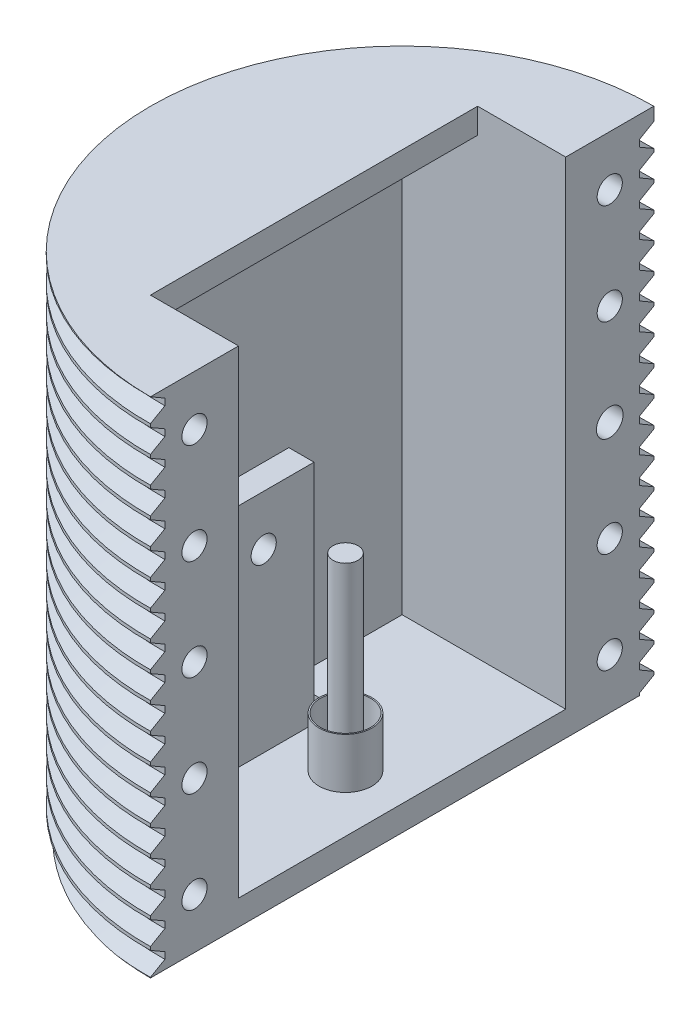
SolidWorks part; units mm, degrees
material "PP Kopolimer"
ref_plane "Front Plane" through (0, 0, 0) normal (0, 0, 1) x (1, 0, 0)
ref_plane "Top Plane" through (0, 0, 0) normal (0, 1, 0) x (1, 0, 0)
ref_plane "Right Plane" through (0, 0, 0) normal (1, 0, 0) x (0, 0, -1)
sketch "Szkic1" plane through (0, 0, 0) normal (0, 1, 0) x (1, 0, 0)
  line L1 (-5, -10) -> (5, -10)
  line L2 (-5, -10) -> (-5, 10)
  line L3 (-5, 10) -> (5, 10)
  line L4 (5, -10) -> (5, 10)
  line L5 (-5, -10) -> (5, 10) construction
  line L6 (-5, 10) -> (5, -10) construction
  point P0 (0, 0)
extrude "Dodanie-wyciągnięcie2" add sketch "Szkic1" along normal blind 1 contours L4 L3 L2 L1
sketch "Szkic2" plane through (0, 1, 0) normal (0, 1, 0) x (1, 0, 0)
  line L1 (-0.5, -2) -> (0.5, -2)
  line L2 (-0.5, -2) -> (-0.5, 2)
  line L3 (-0.5, 2) -> (0.5, 2)
  line L4 (0.5, -2) -> (0.5, 2)
  line L5 (-0.5, -2) -> (0.5, 2) construction
  line L6 (-0.5, 2) -> (0.5, -2) construction
  point P0 (0, 0)
extrude "Wytnij-wyciągnięcie1" cut sketch "Szkic2" against normal blind 1
sketch "Szkic3" plane through (0, 1, 0) normal (0, 1, 0) x (1, 0, 0)
  line L2 (-5, 10) -> (-5, -10)
  line L4 (-1.5, 6.5) -> (-1.5, -6.5)
  line L5 (5, -10) -> (5, 10) construction
  line L8 (-1.5, -6.5) -> (5, -6.5)
  line L9 (5, -10) -> (5, -6.5)
  line L10 (-5, 10) -> (5, 10)
  line L12 (5, 10) -> (5, 6.5)
  line L13 (5, 6.5) -> (-1.5, 6.5)
  line L15 (-5, -10) -> (5, -10)
extrude "Dodanie-wyciągnięcie3" add sketch "Szkic3" along normal blind 19
sketch "Szkic4" plane through (0, 1, 0) normal (0, 1, 0) x (1, 0, 0)
  line L0 (-1.5, -6.5) -> (-1.5, 6.5) construction
  line L1 (-0.5, 2) -> (-1.5, 2)
  line L2 (-0.5, 2) -> (-0.5, -2)
  line L3 (-0.5, -2) -> (-1.5, -2)
  line L4 (-1.5, 2) -> (-1.5, -2)
extrude "Dodanie-wyciągnięcie5" add sketch "Szkic4" along normal blind 8 contours L1 L4 L3 L2
sketch "Szkic7" plane through (-0.5, 0, 0) normal (1, 0, 0) x (0, 0, -1)
  line L0 (0, 9) -> (0, 7) construction
  line L1 (2, 9) -> (-2, 9) construction
  circle A0 centre (0, 7) radius 0.5
extrude "Wytnij-wyciągnięcie2" cut sketch "Szkic7" against normal blind 1 contours A0
sketch "Szkic8" plane through (0, 1, 0) normal (0, 1, 0) x (1, 0, 0)
  line L0 (0.5, 0) -> (5, 0) construction
  line L1 (0.5, -2) -> (0.5, 2) construction
  line L2 (5, -6.5) -> (5, 6.5) construction
  circle A0 centre (2.75, 0) radius 0.5
extrude "Dodanie-wyciągnięcie6" add sketch "Szkic8" along normal blind 7.5
sketch "Szkic13" plane through (-1.5, 0, 0) normal (1, 0, 0) x (0, 0, -1)
  line L0 (-6.5, 20) -> (-6.5, 1) construction
  line L1 (6.5, 20) -> (-6.5, 20)
  line L2 (6.5, 20) -> (6.5, 19)
  line L3 (6.5, 19) -> (-6.5, 19)
  line L4 (-6.5, 20) -> (-6.5, 19)
extrude "Dodanie-wyciągnięcie8" add sketch "Szkic13" along normal blind 3
fillet "Zaokrąglenie2" radius 10 2 edges at (-5, 10, 10) (-5, 10, -10)
sketch "Szkic16" plane through (5, 0, 0) normal (1, 0, 0) x (0, 0, -1)
  line L0 (-8.25, 20) -> (-8.25, 18) construction
  line L1 (-10, 20) -> (-6.5, 20) construction
  line L2 (-8.25, 18) -> (-8.25, 14) construction
  line L3 (-8.25, 14) -> (-8.25, 10) construction
  line L4 (-8.25, 10) -> (-8.25, 6) construction
  line L5 (-8.25, 6) -> (-8.25, 2) construction
  line L6 (-8.25, 2) -> (-8.25, 0) construction
  line L7 (-10, 0) -> (10, 0) construction
  line L8 (8.25, 20) -> (8.25, 18) construction
  line L9 (6.5, 20) -> (10, 20) construction
  line L10 (8.25, 18) -> (8.25, 14) construction
  line L11 (8.25, 14) -> (8.25, 10) construction
  line L12 (8.25, 10) -> (8.25, 6) construction
  line L13 (8.25, 6) -> (8.25, 2) construction
  line L14 (8.25, 2) -> (8.25, 0) construction
  circle A0 centre (-8.25, 18) radius 0.5
  circle A1 centre (-8.25, 14) radius 0.5
  circle A2 centre (-8.25, 10) radius 0.5
  circle A3 centre (-8.25, 6) radius 0.5
  circle A4 centre (-8.25, 2) radius 0.5
  circle A5 centre (8.25, 18) radius 0.5
  circle A6 centre (8.25, 14) radius 0.5
  circle A7 centre (8.25, 10) radius 0.53
  circle A8 centre (8.25, 6) radius 0.5
  circle A9 centre (8.25, 2) radius 0.5
extrude "Wytnij-wyciągnięcie3" cut sketch "Szkic16" against normal blind 2
thread "Gwint1" pitch 1.0583 method cut profile "Profil gwintu1" start angle 270, offset 0, length 20, pitch 1.0583, diameter 20
ref_plane "Płaszczyzna1" through (5, 20, 10) normal (1, 0, 0) x (0, 0, 1)
sketch "Profil gwintu1" plane through (5, 20, 10) normal (1, 0, 0) x (0, 0, 1)
  line L0 (0, 0) -> (0, 1.0583) construction
  line L11 (0, 0) -> (0, 0.926)
  line L12 (0, 0.926) -> (-0.5728, 0.5953)
  line L13 (-0.5728, 0.5953) -> (-0.5728, 0.3307)
  line L15 (-0.5728, 0.3307) -> (0, 0)
  line L17 (-0.5728, 0.463) -> (0, 0.463) construction
  point P2 (0, 0)
  dimension "Pitch" = 1.0583
  dimension "Profile_Angle" = 60
  dimension "Profile_Land" = 0.2646
  dimension "Profile_Height" = 0.5728
sketch "Szkic17" plane through (0, 1, 0) normal (0, 1, 0) x (1, 0, 0)
  circle A0 centre (2.75, 0) radius 1
  circle A1 centre (2.75, 0) radius 1.05
extrude "Dodanie-wyciągnięcie9" add sketch "Szkic17" along normal blind 2
